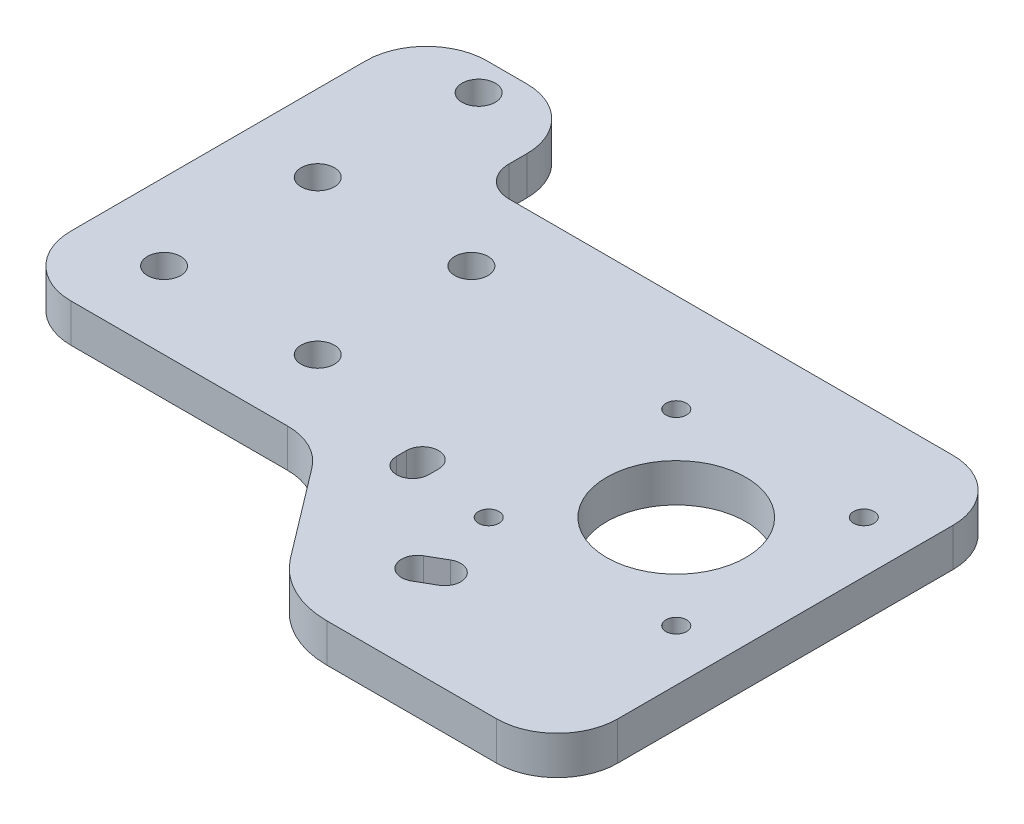
SolidWorks part; units mm, degrees
ref_plane "Front" through (0, 0, 0) normal (0, 0, 1) x (1, 0, 0)
ref_plane "Top" through (0, 0, 0) normal (0, 1, 0) x (1, 0, 0)
ref_plane "Right" through (0, 0, 0) normal (1, 0, 0) x (0, 0, -1)
sketch "Sketch1" plane through (0, 0, 0) normal (0, 1, 0) x (1, 0, 0)
  line L0 (0, 0) -> (89.6212, 0) construction
  line L1 (25.4, -25.4) -> (-25.4, -25.4)
  line L2 (25.4, -25.4) -> (25.4, 25.4) construction
  line L3 (25.4, 25.4) -> (-25.4, 25.4) construction
  line L4 (-25.4, -25.4) -> (-25.4, 25.4)
  line L5 (25.4, -25.4) -> (-25.4, 25.4) construction
  line L6 (25.4, 25.4) -> (-25.4, -25.4) construction
  line L7 (1.2, 25.4) -> (1.2, 76.2) construction
  line L8 (-12.7, 25.4) -> (-12.7, -25.4) construction
  line L9 (12.7, -25.4) -> (12.7, 25.4) construction
  line L10 (0, 0) -> (-25.4, 0) construction
  line L11 (-12.7, 0) -> (-12.7, 25.4) construction
  line L12 (-12.7, 12.7) -> (12.7, 12.7) construction
  line L13 (38.1, -41.4) -> (89.6212, -41.4) construction
  line L14 (86.6212, -27.36) -> (44.6212, -27.36) construction
  line L15 (86.6212, -27.36) -> (86.6212, 14.64) construction
  line L16 (86.6212, 14.64) -> (44.6212, 14.64) construction
  line L17 (44.6212, -27.36) -> (44.6212, 14.64) construction
  line L18 (86.6212, -27.36) -> (44.6212, 14.64) construction
  line L19 (86.6212, 14.64) -> (44.6212, -27.36) construction
  line L20 (81.1212, -21.86) -> (50.1212, -21.86) construction
  line L21 (81.1212, -21.86) -> (81.1212, 9.14) construction
  line L22 (81.1212, 9.14) -> (50.1212, 9.14) construction
  line L23 (50.1212, -21.86) -> (50.1212, 9.14) construction
  line L24 (81.1212, -21.86) -> (50.1212, 9.14) construction
  line L25 (81.1212, 9.14) -> (50.1212, -21.86) construction
  line L26 (89.6212, -41.4) -> (89.6212, 0) construction
  line L27 (36.4, -12.72) -> (65.6212, -12.72) construction
  line L28 (35.1664, -25.3192) -> (52.7755, -28.8008) construction
  line L29 (25.4, -25.4) -> (39.5919, -44.1062)
  line L30 (65.6212, 0) -> (0, 0) construction
  line L31 (1.2, 76.2) -> (-49.6, 76.2) construction
  line L32 (51.5419, -50.04) -> (89.6212, -50.04)
  line L33 (89.6212, -50.04) -> (89.6212, 25.4)
  line L34 (89.6212, 25.4) -> (25.4, 25.4)
  line L35 (36.4, -19.08) -> (36.4, -20.72) construction
  line L36 (51.5419, -35.04) -> (54.3783, -33.4) construction
  line L37 (51.5419, -35.04) -> (51.5419, -50.04) construction
  line L38 (-49.6, 76.2) -> (-49.6, 25.4) construction
  line L39 (-49.6, -25.4) -> (-25.4, -25.4) construction
  line L40 (-49.6, 25.4) -> (-25.4, 25.4) construction
  line L41 (-11.5, 25.4) -> (-11.5, 76.2) construction
  line L42 (-25.4, 25.4) -> (-25.4, 43.35)
  line L43 (-25.4, 43.35) -> (1.2, 43.35)
  line L44 (1.2, 43.35) -> (1.2, 25.4)
  line L45 (1.2, 25.4) -> (25.4, 25.4)
  circle A0 centre (-12.7, 12.7) radius 2.5 construction
  circle A1 centre (12.7, 12.7) radius 2.5 construction
  circle A2 centre (-12.7, -12.7) radius 2.5 construction
  circle A3 centre (12.7, -12.7) radius 2.5 construction
  circle A4 centre (65.6212, -6.36) radius 6.36 construction
  circle A5 centre (65.6212, -6.36) radius 11 construction
  circle A6 centre (50.1212, 9.14) radius 1.5 construction
  circle A7 centre (81.1212, 9.14) radius 1.5 construction
  circle A8 centre (81.1212, -21.86) radius 1.5 construction
  circle A9 centre (50.1212, -21.86) radius 1.5 construction
  circle A10 centre (51.5419, -35.04) radius 6.36 construction
  circle A11 centre (51.5419, -35.04) radius 11 construction
  circle A12 centre (36.4, -19.08) radius 6.36 construction
  circle A13 centre (36.4, -19.08) radius 11 construction
  circle A14 centre (50.1212, -21.86) radius 3 construction
  circle A15 centre (-11.5, 38.1) radius 2.5 construction
  circle A16 centre (-11.5, 38.1) radius 5.25 construction
  circle A19 centre (36.4, -19.08) radius 2.5 construction
  circle A20 centre (51.5419, -35.04) radius 2.5 construction
  circle A21 centre (65.6212, -6.36) radius 11 construction
  arc A22 (39.5919, -44.1062) -> (51.5419, -50.04) centre (51.5419, -35.04) ccw
  circle A23 centre (36.4, -20.72) radius 8 construction
  circle A24 centre (36.4, -20.72) radius 11 construction
  circle A25 centre (54.3783, -33.4) radius 8 construction
  circle A26 centre (54.3783, -33.4) radius 11 construction
  point P0 (0, 0)
  dimension "D6" = 5
  dimension "D7" = 12.72
  dimension "D9" = 22
  dimension "D11" = 3
  dimension "D12" = 16
  dimension "D13" = 6
  dimension "D16" = 12.7
  dimension "D17" = 5
  dimension "D18" = 22
  dimension "D20" = 16
  dimension "D21" = 4
  dimension "D23" = 10.5
  dimension "D1" = 50.8
  dimension "D2" = 50.8
  dimension "D3" = 50.8
  dimension "D4" = 12.7
  dimension "D5" = 25.4
  dimension "D8" = 42
  dimension "D10" = 31
  dimension "D14" = 50.8
  dimension "D15" = 24.2
  dimension "D19" = 3
  dimension "D22" = 12.7
extrude "Boss-Extrude1" add sketch "Sketch1" along normal blind 6.35
hole_wizard "M5 Clearance Hole1" positions "Sketch3" profile "Sketch2" hole size "M5" standard "ISO" end condition through all
sketch "Sketch3" plane through (0, 6.35, 0) normal (0, 1, 0) x (1, 0, 0)
  point P0 (-12.7, 12.7)
  point P3 (12.7, 12.7)
  point P6 (12.7, -12.7)
  point P9 (-12.7, -12.7)
  point P15 (-11.5, 38.1)
sketch "Sketch2" plane through (-12.7, 6.35, -12.7) normal (1, 0, 0) x (0, 0, 1)
  line L0 (0, 0) -> (0, 6.35)
  line L1 (0, 6.35) -> (2.75, 6.35)
  line L2 (2.75, 6.35) -> (2.75, 0)
  line L5 (2.75, 0) -> (0, 0)
  line L11 (0, -6.35) -> (0, 107.95) construction
  dimension "Thru Hole Dia." = 5.5
  dimension "Thru Hole Depth" = 6.35
sketch "Sketch7" plane through (0, 6.35, 0) normal (0, 1, 0) x (1, 0, 0)
  line L0 (36.4, -19.08) -> (36.4, -20.72) construction
  line L1 (54.3783, -33.4) -> (51.5419, -35.04) construction
  line L2 (53.0518, -31.1059) -> (50.2155, -32.7459)
  line L3 (33.75, -19.08) -> (33.75, -20.72)
  line L4 (55.7047, -35.6941) -> (52.8684, -37.3341)
  line L5 (39.05, -19.08) -> (39.05, -20.72)
  arc A0 (53.0518, -31.1059) -> (55.7047, -35.6941) centre (54.3783, -33.4) cw
  arc A1 (50.2155, -32.7459) -> (52.8684, -37.3341) centre (51.5419, -35.04) ccw
  arc A2 (33.75, -19.08) -> (39.05, -19.08) centre (36.4, -19.08) cw
  arc A3 (33.75, -20.72) -> (39.05, -20.72) centre (36.4, -20.72) ccw
  dimension "D1" = 2.65
  dimension "D2" = 2.65
extrude "Cut-Extrude2" cut sketch "Sketch7" against normal through all
fillet "Fillet1" radius 10 6 edges at (89.6212, 3.175, 50.04) (89.6212, 3.175, -25.4) (25.4, 3.175, 25.4) (-25.4, 3.175, 25.4) (-25.4, 3.175, -43.35) (1.2, 3.175, -43.35)
hole_wizard "M3 Clearance Hole1" positions "Sketch9" profile "Sketch8" hole size "M3" standard "ISO" end condition through all
sketch "Sketch9" plane through (0, 6.35, 0) normal (0, 1, 0) x (1, 0, 0)
  point P0 (50.1212, 9.14)
  point P3 (81.1212, 9.14)
  point P6 (81.1212, -21.86)
  point P9 (50.1212, -21.86)
sketch "Sketch8" plane through (50.1212, 6.35, -9.14) normal (1, 0, 0) x (0, 0, 1)
  line L0 (0, 0) -> (0, 6.35)
  line L1 (0, 6.35) -> (1.7, 6.35)
  line L2 (1.7, 6.35) -> (1.7, 0)
  line L5 (1.7, 0) -> (0, 0)
  line L11 (0, -6.35) -> (0, 107.95) construction
  dimension "Thru Hole Dia." = 3.4
  dimension "Thru Hole Depth" = 6.35
sketch "Sketch10" plane through (0, 6.35, 0) normal (0, 1, 0) x (1, 0, 0)
  circle A0 centre (65.6212, -6.36) radius 11.5
  dimension "D1" = 23
extrude "Cut-Extrude3" cut sketch "Sketch10" against normal through all
fillet "Fillet2" radius 5 1 edges at (1.2, 3.175, -25.4)
